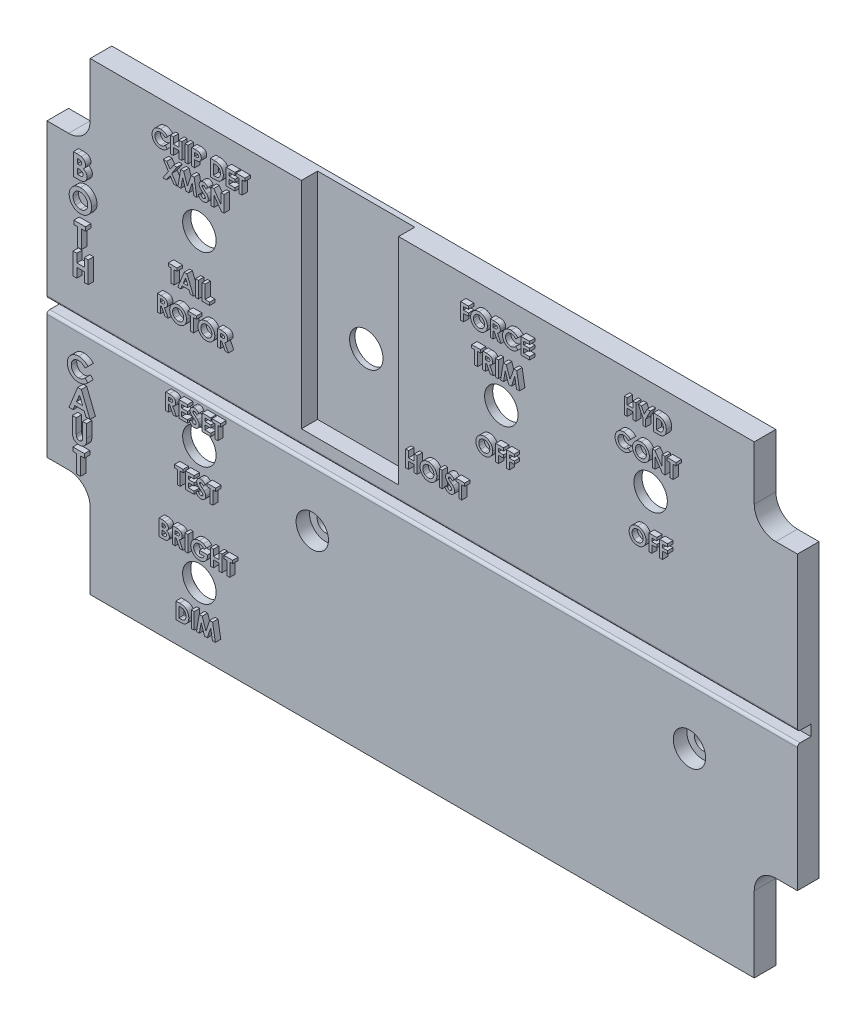
SolidWorks part; units mm, degrees
ref_plane "Front Plane" through (0, 0, 0) normal (0, 0, 1) x (1, 0, 0)
ref_plane "Top Plane" through (0, 0, 0) normal (0, 1, 0) x (1, 0, 0)
ref_plane "Right Plane" through (0, 0, 0) normal (1, 0, 0) x (0, 0, -1)
sketch "Sketch1" plane through (0, 0, 0) normal (0, 0, 1) x (1, 0, 0)
  line L1 (8, 3.6454) -> (131, 3.6454)
  line L2 (0, 21.6454) -> (0, 75.6454)
  line L3 (8, 89.6454) -> (131, 89.6454)
  line L4 (139, 21.6454) -> (139, 75.6454)
  line L13 (8, 89.6454) -> (8, 79.6454)
  line L14 (4, 75.6454) -> (0, 75.6454)
  line L15 (8, 3.6454) -> (8, 17.6454)
  line L16 (4, 21.6454) -> (0, 21.6454)
  line L17 (131, 89.6454) -> (131, 79.6454)
  line L18 (135, 75.6454) -> (139, 75.6454)
  line L19 (131, 3.6454) -> (131, 17.6454)
  line L20 (135, 21.6454) -> (139, 21.6454)
  line L23 (0, 0) -> (0, 87.0008) construction
  arc A8 (8, 17.6454) -> (4, 21.6454) centre (4, 17.6454) ccw
  arc A9 (8, 79.6454) -> (4, 75.6454) centre (4, 79.6454) cw
  arc A11 (131, 17.6454) -> (135, 21.6454) centre (135, 17.6454) cw
  arc A12 (131, 79.6454) -> (135, 75.6454) centre (135, 79.6454) ccw
  circle A47 centre (49.1366, 34.4511) radius 1.6 construction
  circle A48 centre (28.228, 15.6399) radius 3.1 construction
  circle A49 centre (28.228, 37.6399) radius 3.1 construction
  circle A50 centre (119, 34.4511) radius 1.6 construction
  circle A51 centre (111.8065, 72.0649) radius 3.1 construction
  circle A52 centre (84.1546, 72.0649) radius 3.1 construction
  circle A53 centre (56.1418, 65.6454) radius 3.1 construction
  circle A54 centre (28.228, 72.0649) radius 3.1 construction
  circle A55 centre (49.1366, 34.4511) radius 1.6
  circle A56 centre (28.228, 15.6399) radius 3.1
  circle A57 centre (28.228, 37.6399) radius 3.1
  circle A58 centre (119, 34.4511) radius 1.6
  circle A59 centre (111.8065, 72.0649) radius 3.1
  circle A60 centre (84.1546, 72.0649) radius 3.1
  circle A61 centre (56.1418, 65.6454) radius 3.1
  circle A62 centre (28.228, 72.0649) radius 3.1
  point P21 (131, 21.6454)
  point P25 (8, 75.6454)
  point P40 (131, 75.6454)
  dimension "D3" = 18
  dimension "D4" = 14
  dimension "D5" = 8
  dimension "D7" = 86
  dimension "D11" = 8
  dimension "D15" = 123
  dimension "D16" = 139
  dimension "D22" = 8
  dimension "D9" = 8
extrude "Boss-Extrude1" add sketch "Sketch1" along normal blind 4
sketch "Sketch8" plane through (0, 0, 4) normal (0, 0, 1) x (1, 0, 0)
  line L2 (65.122, 89.6454) -> (47.1217, 89.6454)
  line L3 (65.122, 89.6454) -> (65.122, 49.8046)
  line L4 (65.122, 49.8046) -> (47.1217, 49.8046)
  line L5 (47.1217, 89.6454) -> (47.1217, 49.8046)
extrude "Switch cover base" cut sketch "Sketch8" against normal blind 3
sketch "Sketch4" plane through (0, 0, 4) normal (0, 0, 1) x (1, 0, 0)
  line L0 (8, 54.5551) -> (8, 14.5758) construction
  line L1 (8, 89.6454) -> (8, 79.6454) construction
  line L2 (-3.2263, 22.7284) -> (14.9404, 22.7284) construction
  line L3 (73.2866, 82.9664) -> (95.0227, 82.9664) construction
  line L4 (-3.2263, 37.7284) -> (14.9404, 37.7284) construction
  line L5 (-3.2263, 32.7284) -> (14.9404, 32.7284) construction
  line L6 (-3.2263, 27.7284) -> (14.9404, 27.7284) construction
  line L7 (5, 54.5551) -> (5, 14.5758) construction
  line L8 (105.7135, 82.9664) -> (117.8994, 82.9664) construction
  circle A1 centre (84.1546, 72.0649) radius 3.1 construction
  circle A2 centre (84.1546, 72.0649) radius 3.1 construction
  circle A3 centre (111.8065, 72.0649) radius 3.1 construction
  circle A4 centre (111.8065, 72.0649) radius 3.1 construction
  text T0 "<b>C</b>" font "Century Gothic" height 4
  text T1 "<b>B</b>" font "Century Gothic" height 4
  text T2 "<b>TEST</b>" font "Century Gothic" height 3
  text T3 "<b>BRIGHT</b>" font "Century Gothic" height 3
  text T4 "<b>FORCE</b>\r\n<b>TRIM</b>" font "Century Gothic" height 3
  text T5 "<b>T</b>" font "Century Gothic" height 4
  text T6 "<b>  TAIL</b>\r\n<b>ROTOR</b>" font "Century Gothic" height 3
  text T7 "<b>HOIST</b>" font "Century Gothic" height 3
  text T8 "<b>CHIP DET</b>" font "Century Gothic" height 3
  text T9 "<b>A</b>" font "Century Gothic" height 4
  text T10 "<b>U</b>" font "Century Gothic" height 4
  text T11 "<b>XMSN</b>" font "Century Gothic" height 3
  text T12 "<b>OFF</b>" font "Century Gothic" height 3
  text T13 "<b>OFF</b>" font "Century Gothic" height 3
  text T14 "<b>DIM</b>" font "Century Gothic" height 3
  text T15 "<b>RESET</b>" font "Century Gothic" height 3
  text T16 "<b>HYD</b>\r\n<b>CONT</b>" font "Century Gothic" height 3
  text T17 "<b>O</b>" font "Century Gothic" height 4
  text T18 "<b>T</b>" font "Century Gothic" height 4
  text T19 "<b>H</b>" font "Century Gothic" height 4
  point P29 (111.8065, 82.9664)
  point P31 (84.1546, 82.9664)
  dimension "D1" = 3
  dimension "D2" = 5
  dimension "D3" = 5
  dimension "D4" = 5
extrude "Textos" add sketch "Sketch4" along normal blind 1
sketch "Sketch9" plane through (0, 0, 0) normal (0, 0, -1) x (-1, 0, 0)
  circle A10 centre (-111.8065, 72.0649) radius 6.6
  circle A11 centre (-84.1546, 72.0649) radius 6.6
  circle A12 centre (-28.228, 72.0649) radius 6.6
  circle A13 centre (-28.228, 37.6399) radius 6.6
  circle A14 centre (-28.228, 15.6399) radius 6.6
  dimension "D1" = 13.2
extrude "Back holes" cut sketch "Sketch9" against normal blind 2.5
sketch "Sketch10" plane through (0, 0, 4) normal (0, 0, 1) x (1, 0, 0)
  line L0 (0, 75.6454) -> (0, 21.6454) construction
  line L1 (0, 47.1167) -> (139, 47.1167)
  line L2 (0, 47.1167) -> (0, 45.1167)
  line L3 (0, 45.1167) -> (139, 45.1167)
  line L4 (139, 47.1167) -> (139, 45.1167)
  line L5 (139, 21.6454) -> (139, 75.6454) construction
  dimension "D1" = 2
extrude "Division interna panel" cut sketch "Sketch10" against normal blind 2.5
fillet "Fillet1" radius 0.5 2 edges at (69.5, 45.1167, 4) (69.5, 47.1167, 4)
sketch "Sketch12" plane through (0, 0, 4) normal (0, 0, 1) x (1, 0, 0)
  circle A0 centre (49.1366, 34.4511) radius 3
  circle A1 centre (119, 34.4511) radius 3
  dimension "D1" = 6
extrude "Cut-Extrude7" cut sketch "Sketch12" against normal blind 2.5
